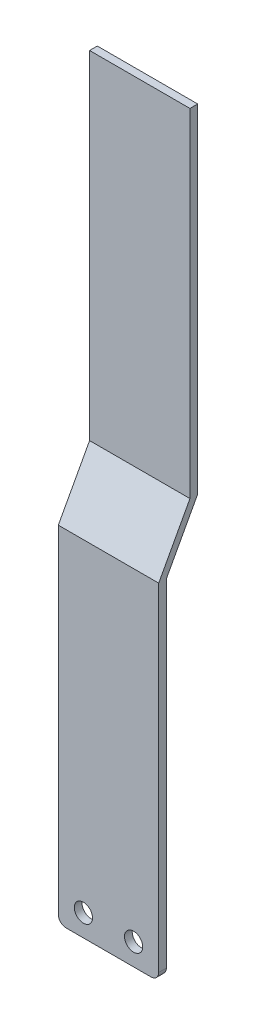
SolidWorks part; units mm, degrees
ref_plane "Front Plane" through (0, 0, 0) normal (0, 0, 1) x (1, 0, 0)
ref_plane "Top Plane" through (0, 0, 0) normal (0, 1, 0) x (1, 0, 0)
ref_plane "Right Plane" through (0, 0, 0) normal (1, 0, 0) x (0, 0, -1)
sketch "Sketch5" plane through (0, 0, 0) normal (0, 0, 1) x (1, 0, 0)
  line L5 (-16.129, 49.4356) -> (-16.129, 151.8049)
  line L6 (-16.129, 151.8049) -> (16.8766, 151.8049)
  line L7 (-13.589, 38.4002) -> (14.3366, 38.4002)
  line L8 (-16.129, 40.9402) -> (-16.129, 49.4356)
  line L9 (16.8766, 40.9402) -> (16.8766, 49.4356)
  line L10 (-17.7882, 151.8049) -> (26.6704, 151.8049) construction
  line L11 (16.8766, 151.8049) -> (16.8766, 49.4356)
  circle A6 centre (-7.8776, 45.5871) radius 2.9925
  circle A7 centre (8.6252, 45.5871) radius 2.9925
  arc A8 (-16.129, 40.9402) -> (-13.589, 38.4002) centre (-13.589, 40.9402) ccw
  arc A9 (14.3366, 38.4002) -> (16.8766, 40.9402) centre (14.3366, 40.9402) ccw
extrude "Boss-Extrude2" add sketch "Sketch5" along normal blind 2.54
sketch "Sketch7" plane through (16.8766, 0, 0) normal (1, 0, 0) x (0, 0, -1)
  line L1 (-2.54, 151.8049) -> (0, 151.8049)
  line L3 (10.2792, 281.8281) -> (7.7392, 281.8281)
  line L9 (-2.54, 151.8049) -> (7.7392, 170.7437)
  line L10 (0, 151.8049) -> (10.2792, 170.7437)
  line L12 (10.2792, 170.7437) -> (10.2792, 281.8281)
  line L13 (7.7392, 170.7437) -> (7.7392, 281.8281)
extrude "Boss-Extrude3" add sketch "Sketch7" against normal up to vertex (33.0057 mm away) up to point (-16.129, 151.8049, 2.54)
